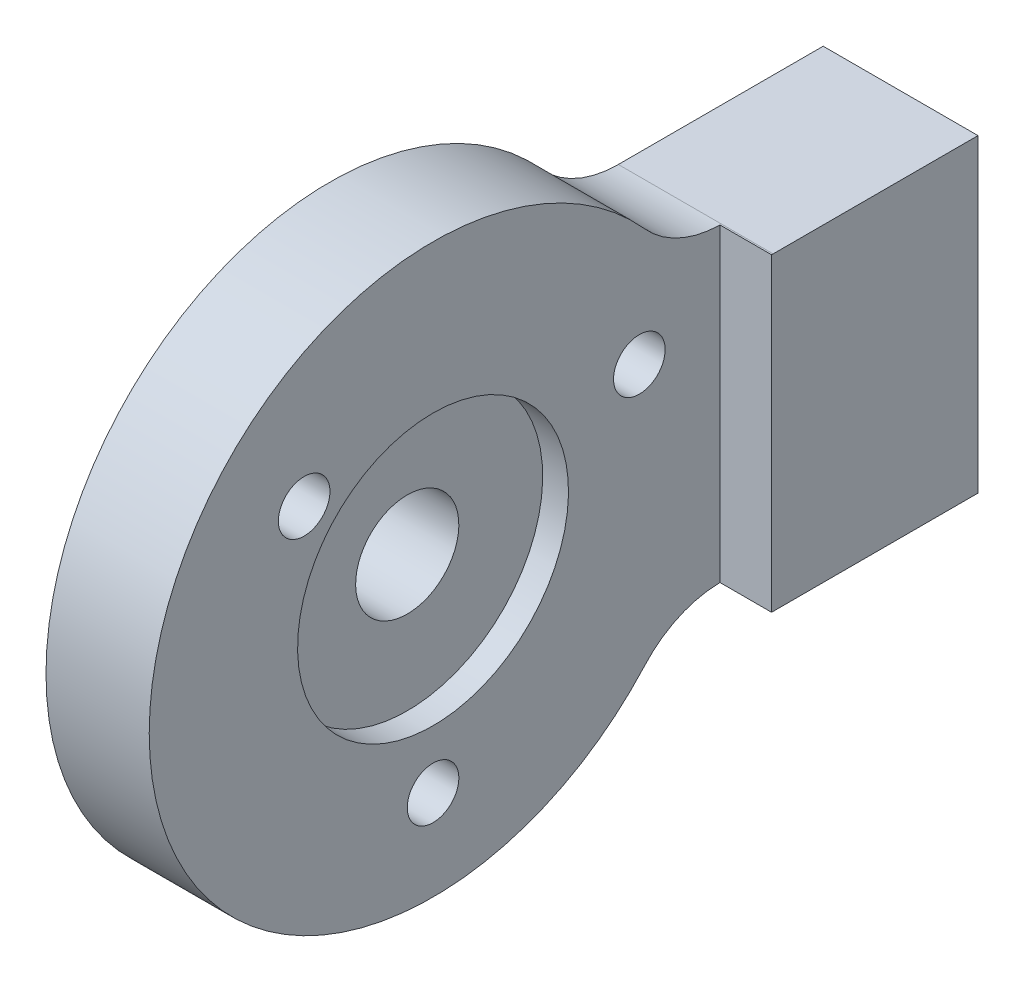
SolidWorks part; units mm, degrees
note: '?' marks a value the reader was unsure of.
ref_plane "Front" through (0, 0, 0) normal (0, 0, 1) x (1, 0, 0)
ref_plane "Top" through (0, 0, 0) normal (0, 1, 0) x (1, 0, 0)
ref_plane "Right" through (0, 0, 0) normal (1, 0, 0) x (0, 0, -1)
sketch "Sketch1" plane through (0, 0, 0) normal (0, 0, 1) x (1, 0, 0)
  line L1 (-2, 6) -> (4, 6)
  line L2 (-2, 6) -> (-2, -6)
  line L3 (-2, -6) -> (4, -6)
  line L4 (4, 6) -> (4, -6)
  dimension "D1" = 6
  dimension "D2" = 6
  dimension "D3" = 2
  dimension "D4" = 4
extrude "Extrude1" add sketch "Sketch1" along normal blind 8
sketch "Sketch2" plane through (0, 0, 0) normal (0, 0, -1) x (-1, 0, 0)
  line L0 (-4, 6) -> (2, 6) construction
  line L1 (2, -6) -> (-4, -6) construction
  line L2 (-4, -6) -> (-4, 6) construction
  circle A0 centre (-1, 3) radius 1.25
  circle A1 centre (-1, -3) radius 1.25
  dimension "D2" = 2.5
  dimension "D3" = 2.5
  dimension "D1" = 3
  dimension "D4" = 3
  dimension "D5" = 3
sketch "Sketch3" plane through (0, 0, 8) normal (0, 0, 1) x (1, 0, 0)
  line L1 (-2, 4.3) -> (2, 4.3)
  line L2 (-2, 4.3) -> (-2, -4.3)
  line L3 (-2, -4.3) -> (2, -4.3)
  line L4 (2, 4.3) -> (2, -4.3)
  dimension "D1" = 2
  dimension "D2" = 2
  dimension "D3" = 4.3
  dimension "D4" = 4.3
extrude "Extrude2" add sketch "Sketch3" along normal blind 1
extrude "Extrude3" cut sketch "Sketch2" against normal blind 6
cosmetic thread "Hole Thread1" parameters "D1"=4.5, "D2"=3
cosmetic thread "Hole Thread2" parameters "D1"=4.5, "D2"=3
sketch "Sketch4" plane through (2, 0, 0) normal (1, 0, 0) x (0, 0, -1)
  line L0 (-9.9005, 6) -> (-8, 6)
  line L1 (-9, -4.3) -> (-9, 4.3) construction
  line L2 (-8, 6) -> (-8, -6)
  line L3 (-8, -6) -> (-9.9005, -6)
  arc A0 (-9.9005, 6) -> (-9.9005, -6) centre (-19.12, 0) ccw
  dimension "D2" = 11
  dimension "D1" = 10.12
extrude "Extrude4" add sketch "Sketch4" against normal blind 4
sketch "Sketch8" plane through (2, 0, 0) normal (1, 0, 0) x (0, 0, -1)
  circle A0 centre (-19.12, 0) radius 5.25
  dimension "D1" = 10.5
extrude "Extrude7" cut sketch "Sketch8" against normal blind 1
ref_axis "Axis1" through (1, 0, 19.12) along (1, 0, 0)?
sketch "Sketch7" plane through (-2, 0, 0) normal (-1, 0, 0) x (0, 0, 1)
  circle A0 centre (19.12, -7.5) radius 1
  circle A2 centre (19.12, 0) radius 5.25 construction
  dimension "D1" = 2
  dimension "D2" = 7.5
extrude "Extrude6" cut sketch "Sketch7" against normal up to surface (4 mm away) up to face at (2, 5.25, 19.12)
pattern_circular "CirPattern1" count 3 over 360 about axis through (0, 0, 18.12) along (1, 0, 0) of "Extrude6"
sketch "Sketch9" plane through (1, 0, 0) normal (1, 0, 0) x (0, 0, -1)
  circle A0 centre (-19.12, 0) radius 2
  dimension "D1" = 4
extrude "Extrude8" cut sketch "Sketch9" against normal up to surface (3 mm away) up to face at (-2, 3.384, 10.2588)
hole_wizard "M3 Tapped Hole1" positions "3DSketch1" profile "Sketch10" tap size "M3" standard "DIN"
sketch3d "3DSketch1"
  line L0 (1, 3, 6) -> (1, 3, 0) construction
  line L1 (1, -3, 6) -> (1, -3, 0) construction
  point P0 (1, 3, 0)
  point P4 (1, -3, 0)
sketch "Sketch10" plane through (1, 3, 0) normal (1, 0, 0) x (0, 1, 0)
  line L0 (0, 0) -> (0, 6.7511)
  line L1 (0, 6.7511) -> (1.25, 6)
  line L2 (1.25, 6) -> (1.25, 0)
  line L5 (1.25, 0) -> (0, 0)
  line L10 (0, 6.7511) -> (-1.25, 6) construction
  line L11 (0, -6.35) -> (0, 107.95) construction
  dimension "Tap Drill Dia." = 2.5
  dimension "Tap Drill Depth" = 6
  dimension "Drill Angle" = 118
fillet "Fillet1" radius 4 2 edges at (0, -6, 9.9005) (0, 6, 9.9005)
